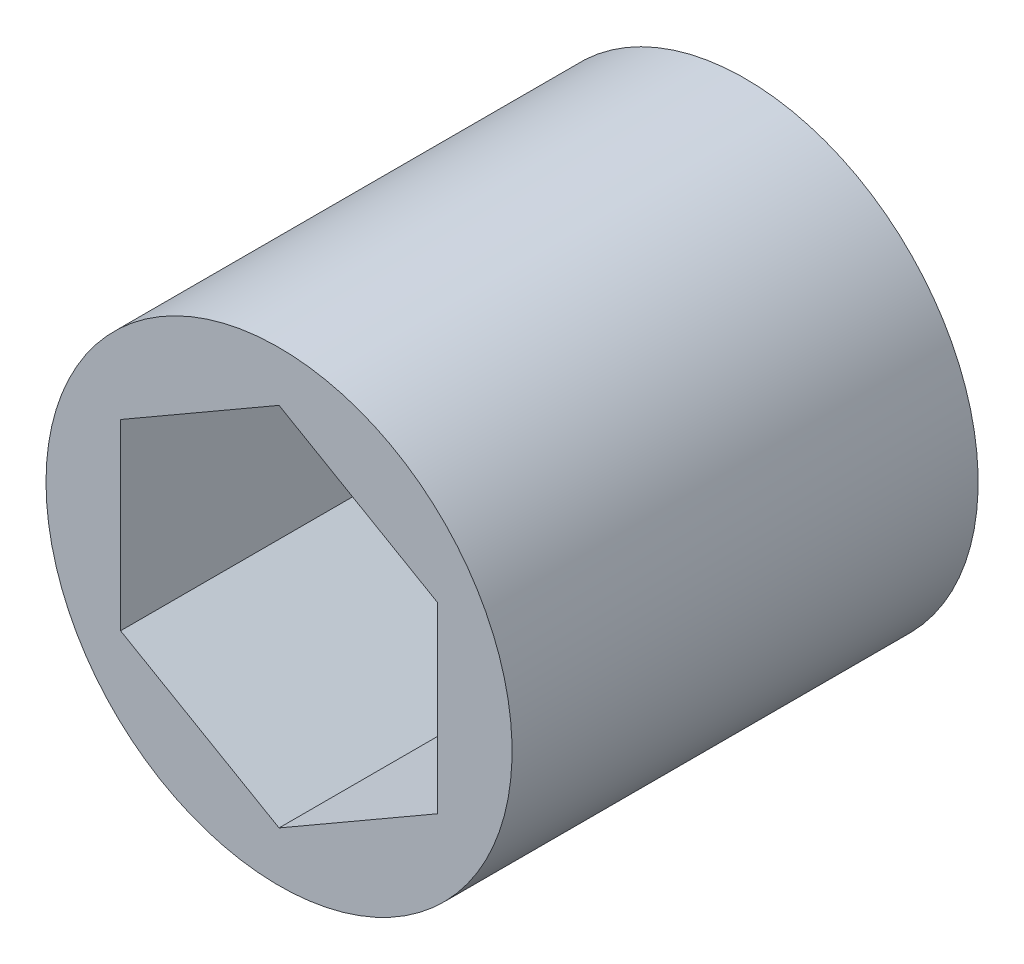
SolidWorks part; units mm, degrees
material "PET"
ref_plane "Front Plane" through (0, 0, 0) normal (0, 0, 1) x (1, 0, 0)
ref_plane "Top Plane" through (0, 0, 0) normal (0, 1, 0) x (1, 0, 0)
ref_plane "Right Plane" through (0, 0, 0) normal (1, 0, 0) x (0, 0, -1)
sketch "Sketch1" plane through (0, 0, 0) normal (0, 0, 1) x (1, 0, 0)
  line L1 (0, 7.479) -> (-6.477, 3.7395)
  line L2 (-6.477, 3.7395) -> (-6.477, -3.7395)
  line L3 (-6.477, -3.7395) -> (0, -7.479)
  line L4 (0, -7.479) -> (6.477, -3.7395)
  line L5 (6.477, -3.7395) -> (6.477, 3.7395)
  line L6 (6.477, 3.7395) -> (0, 7.479)
  circle A0 centre (0, 0) radius 6.477 construction
  circle A1 centre (0, 0) radius 9.525
  dimension "D1" = 12.954
  dimension "D2" = 19.05
extrude "Boss-Extrude1" add sketch "Sketch1" along normal mid plane 19.05
